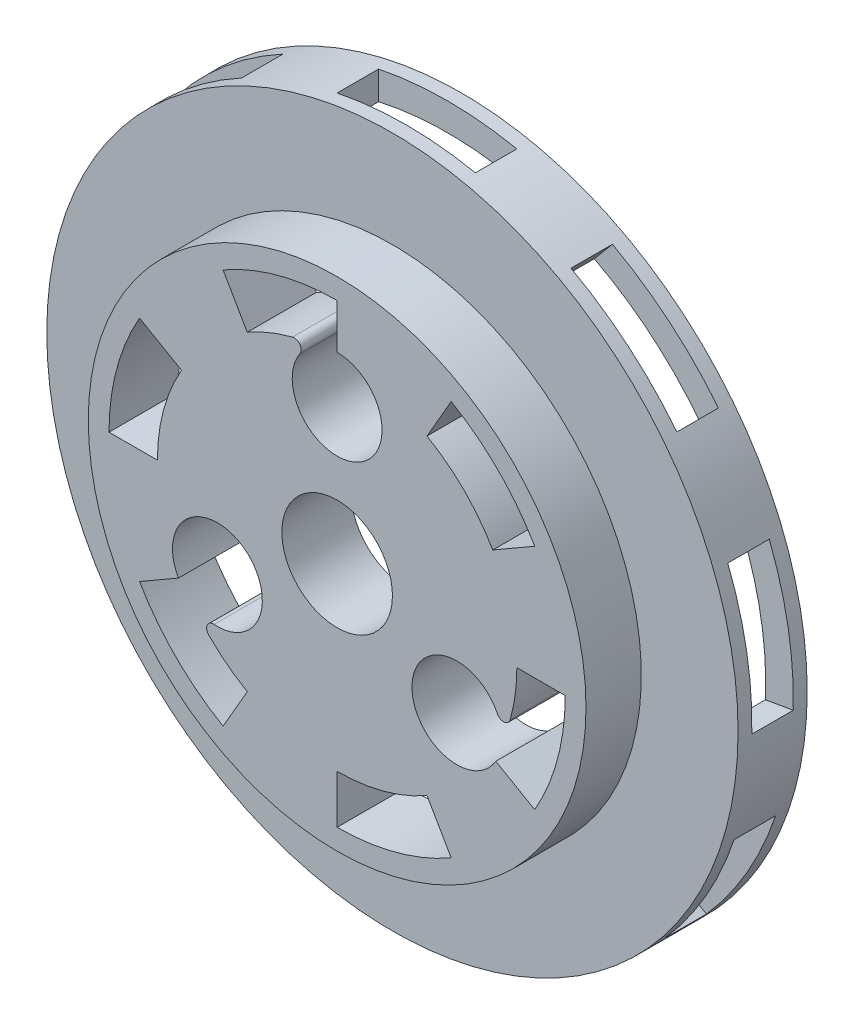
SolidWorks part; units mm, degrees
ref_plane "Plan de face" through (0, 0, 0) normal (0, 0, 1) x (1, 0, 0)
ref_plane "Plan de dessus" through (0, 0, 0) normal (0, 1, 0) x (1, 0, 0)
ref_plane "Plan de droite" through (0, 0, 0) normal (1, 0, 0) x (0, 0, -1)
sketch "Esquisse1" plane through (0, 0, 0) normal (0, 0, 1) x (1, 0, 0)
  circle A0 centre (0, 0) radius 18
  dimension "D1" = 36
extrude "Boss.-Extru.1" add sketch "Esquisse1" along normal blind 4
sketch "Esquisse5" plane through (0, 0, 0) normal (0, 0, -1) x (-1, 0, 0)
  circle A0 centre (0, 0) radius 25
  dimension "D1" = 50
extrude "Boss.-Extru.2" add sketch "Esquisse5" along normal blind 1
sketch "Esquisse2" plane through (0, 0, 4) normal (0, 0, 1) x (1, 0, 0)
  line L0 (0, 13) -> (0, 16.5)
  line L1 (-8.25, 14.2894) -> (-6.5, 11.2583)
  arc A0 (0, 16.5) -> (-8.25, 14.2894) centre (0, 0) ccw
  arc A1 (0, 13) -> (-6.5, 11.2583) centre (0, 0) ccw
  dimension "D1" = 33
  dimension "D2" = 26
  dimension "D3" = 30
extrude "Enlèv. mat.-Extru.1" cut sketch "Esquisse2" against normal through all
sketch "Esquisse4" plane through (0, 0, 4) normal (0, 0, 1) x (1, 0, 0)
  circle A0 centre (0, 0) radius 4
  dimension "D1" = 8
extrude "Enlèv. mat.-Extru.3" cut sketch "Esquisse4" against normal through all
pattern_circular "Répétition circulaire1" count 6 over 360 about axis through (0, 0, 4) along (0, 0, 1) of "Enlèv. mat.-Extru.1"
sketch "Esquisse3" plane through (0, 0, 4) normal (0, 0, 1) x (1, 0, 0)
  circle A0 centre (0, 10) radius 3.25
  dimension "D2" = 6.5
  dimension "D1" = 10
extrude "Enlèv. mat.-Extru.2" cut sketch "Esquisse3" against normal through all
pattern_circular "Répétition circulaire2" count 3 over 360 about axis through (0, 0, 4) along (0, 0, 1) of "Enlèv. mat.-Extru.2"
fillet "Congé1" radius 0.5 3 edges at (11.9022, -5.2285, 1.5) (-10.4791, -7.6934, 1.5) (-1.4231, 12.9219, 1.5)
sketch "Esquisse6" plane through (0, 0, -1) normal (0, 0, -1) x (-1, 0, 0)
  circle A0 centre (0, 0) radius 25
  circle A1 centre (0, 0) radius 23
  circle A2 centre (0, 0) radius 25 construction
  dimension "D1" = 2
extrude "Boss.-Extru.3" add sketch "Esquisse6" along normal blind 4
ref_plane "Plan1" through (0, 25, 0) normal (0, 1, 0) x (1, 0, 0)
sketch "Esquisse7" plane through (0, 25, 0) normal (0, 1, 0) x (1, 0, 0)
  line L2 (0, -4.95) -> (0, 4.95) construction
  line L3 (5, 1) -> (-5, 1)
  line L4 (5, 1) -> (5, 4)
  line L5 (5, 4) -> (-5, 4)
  line L6 (-5, 1) -> (-5, 4)
  line L7 (5, 1) -> (-5, 4) construction
  line L8 (5, 4) -> (-5, 1) construction
  line L9 (25, 5) -> (-25, 5) construction
  point P0 (0, 2.5)
  dimension "D2" = 3
  dimension "D1" = 10
  dimension "D3" = 0
  dimension "D4" = 2.5
extrude "Enlèv. mat.-Extru.4" cut sketch "Esquisse7" against normal blind 4
ref_axis "Axe1" through (0, 0, -1) along (0, 0, 1)
pattern_circular "Répétition circulaire3" count 9 every 40 about axis through (0, 0, -1) along (0, 0, 1) of "Enlèv. mat.-Extru.4"
